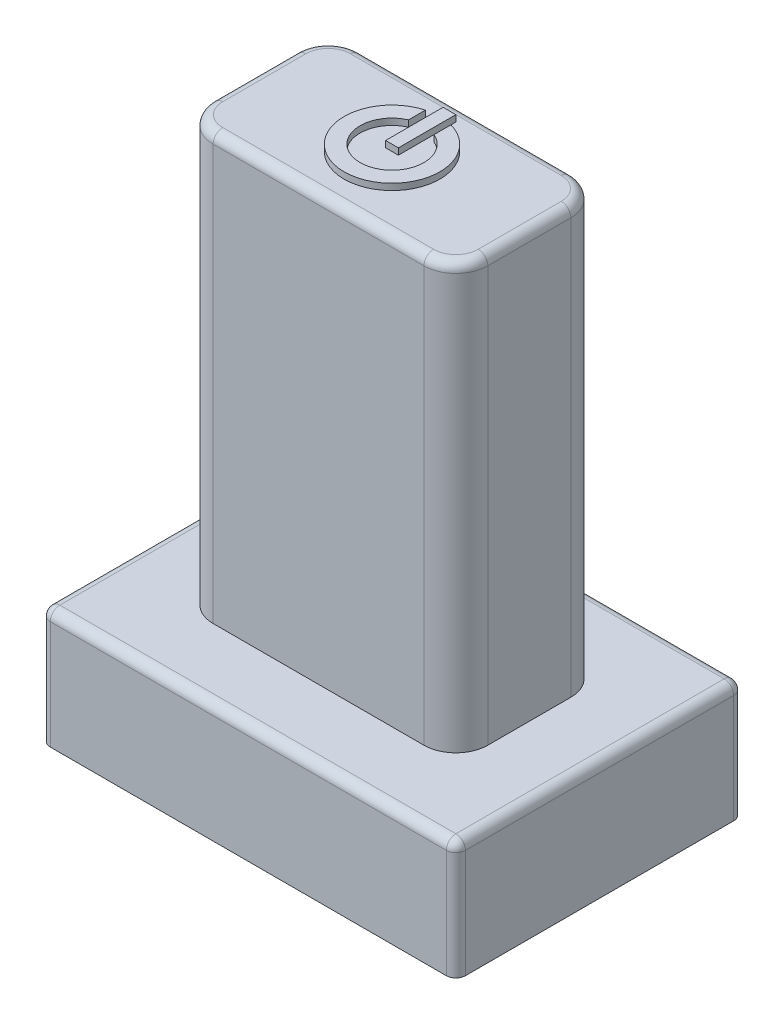
SolidWorks part; units mm, degrees
ref_plane "Front Plane" through (0, 0, 0) normal (0, 0, 1) x (1, 0, 0)
ref_plane "Top Plane" through (0, 0, 0) normal (0, 1, 0) x (1, 0, 0)
ref_plane "Right Plane" through (0, 0, 0) normal (1, 0, 0) x (0, 0, -1)
sketch "草图1" plane through (0, 0, 0) normal (0, 1, 0) x (1, 0, 0)
  line L4 (7.6943, 0.2) -> (16.2943, 0.2)
  line L5 (16.2943, 0.2) -> (16.2943, 4.8)
  line L6 (16.2943, 4.8) -> (7.6943, 4.8)
  line L7 (7.6943, 4.8) -> (7.6943, 0.2)
extrude "凸台-拉伸1" add sketch "草图1" along normal blind 17
sketch "草图2" plane through (0, 0, 0) normal (0, -1, 0) x (1, 0, 0)
  line L0 (5.4943, 2) -> (5.4943, -7)
  line L1 (5.4943, -7) -> (18.4943, -7)
  line L2 (18.4943, -7) -> (18.4943, 2)
  line L3 (18.4943, 2) -> (5.4943, 2)
  line L4 (7.6943, -0.2) -> (7.6943, -4.8)
  line L5 (7.6943, -0.2) -> (7.6943, -4.8)
  line L6 (7.6943, -4.8) -> (16.2943, -4.8)
  line L7 (7.6943, -4.8) -> (16.2943, -4.8)
  line L16 (16.2943, -4.8) -> (16.2943, -0.2)
  line L17 (16.2943, -4.8) -> (16.2943, -0.2)
  line L18 (16.2943, -0.2) -> (7.6943, -0.2)
  line L19 (16.2943, -0.2) -> (7.6943, -0.2)
  dimension "D1" = 0
extrude "凸台-拉伸2" add sketch "草图2" against normal blind 3.7
fillet "圆角1" radius 1 4 edges at (16.2943, 10.35, -4.8) (16.2943, 10.35, -0.2) (7.6943, 10.35, -0.2) (7.6943, 10.35, -4.8)
fillet "圆角2" radius 0.3 16 edges at (7.9872, 17, -0.4929) (7.6943, 17, -2.5) (7.9872, 17, -4.5071) (11.9943, 17, -4.8) (16.0014, 17, -4.5071) (16.2943, 17, -2.5) (16.0014, 17, -0.4929) (11.9943, 17, -0.2) (18.4943, 1.85, 2) (5.4943, 1.85, 2) (18.4943, 1.85, -7) (5.4943, 1.85, -7) (5.4943, 3.7, -2.5) (11.9943, 3.7, 2) (18.4943, 3.7, -2.5) (11.9943, 3.7, -7)
sketch "草图3" plane through (0, 17, 0) normal (0, 1, 0) x (1, 0, 0)
  line L0 (11.9943, 2.5) -> (12.1943, 2.5)
  line L1 (11.9943, 2.5) -> (11.7943, 2.5)
  line L2 (11.7943, 2.5) -> (11.7943, 4.3)
  line L3 (11.7943, 4.3) -> (12.1943, 4.3)
  line L4 (12.1943, 4.3) -> (12.1943, 2.5)
  line L6 (11.5943, 3.4165) -> (11.5943, 3.9457)
  line L8 (12.3943, 3.9457) -> (12.3943, 3.4165)
  arc A0 (11.5943, 3.9457) -> (12.3943, 3.9457) centre (11.9943, 2.5) ccw
  arc A1 (11.5943, 3.4165) -> (12.3943, 3.4165) centre (11.9943, 2.5) ccw
extrude "凸台-拉伸3" add sketch "草图3" along normal blind 0.2
